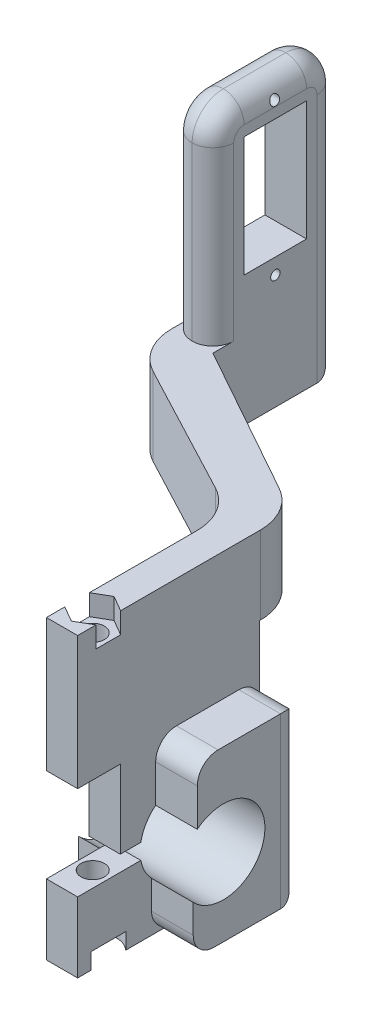
SolidWorks part; units mm, degrees
ref_plane "Front Plane" through (0, 0, 0) normal (0, 0, 1) x (1, 0, 0)
ref_plane "Top Plane" through (0, 0, 0) normal (0, 1, 0) x (1, 0, 0)
ref_plane "Right Plane" through (0, 0, 0) normal (1, 0, 0) x (0, 0, -1)
sketch "Sketch1" plane through (0, 0, 0) normal (1, 0, 0) x (0, 0, -1)
  line L0 (-55.3503, -42.4114) -> (-43.2084, -42.4114)
  line L2 (4.6497, -1.9114) -> (4.6497, 37.0886)
  line L3 (4.6497, 37.0886) -> (28.6497, 37.0886)
  line L4 (10.6497, 31.0886) -> (22.6497, 31.0886)
  line L5 (-27.3711, -35.4334) -> (28.6497, 37.0886) construction
  line L6 (4.6497, 37.0886) -> (-5.2585, -41.9446) construction
  line L7 (-20.3503, -58.9114) -> (-55.3503, -58.9114)
  line L8 (-55.3503, -45.4114) -> (-43.2084, -45.4114)
  line L10 (-55.3503, -58.9114) -> (-55.3503, -45.4114)
  line L11 (10.6497, 31.0886) -> (10.6497, 8.0886)
  line L12 (28.6497, 37.0886) -> (28.6497, -16.9114)
  line L13 (10.6497, 8.0886) -> (22.6497, 8.0886)
  line L14 (22.6497, 31.0886) -> (22.6497, 8.0886)
  line L15 (-55.3503, -42.4114) -> (-55.3503, -28.9114)
  line L18 (28.6497, -16.9114) -> (-20.3503, -16.9114)
  line L19 (4.6497, -1.9114) -> (-55.3503, -1.9114)
  line L20 (-55.3503, -28.9114) -> (-55.3503, -1.9114)
  line L21 (-20.3503, -58.9114) -> (-20.3503, -16.9114)
  arc A0 (-43.2084, -45.4114) -> (-43.2084, -42.4114) centre (-35.3503, -43.9114) ccw
  circle A1 centre (16.6497, 34.0886) radius 0.9
  circle A2 centre (16.6497, 5.0886) radius 0.9
  point P0 (0, 0)
  dimension "D3" = 16
  dimension "D11" = 1.8
  dimension "D12" = 1.8
  dimension "D1" = 30
  dimension "D2" = 15
  dimension "D4" = 35
  dimension "D5" = 20
  dimension "D6" = 24
  dimension "D7" = 12
  dimension "D8" = 6
  dimension "D9" = 6
  dimension "D10" = 23
  dimension "D13" = 3
  dimension "D14" = 3
  dimension "D15" = 6
  dimension "D16" = 6
  dimension "D17" = 13.5
  dimension "D18" = 3
  dimension "D19" = 86
  dimension "D20" = 25
  dimension "D21" = 42
  dimension "D22" = 60
extrude "Boss-Extrude1" add sketch "Sketch1" along normal blind 42
hole_wizard "CBORE for M4 Pan Head Machine Screw2" positions "Sketch6" profile "Sketch5" counterbore size "M4" standard "ANSI Metric" end condition through all
sketch "Sketch6" plane through (0, -58.9114, 0) normal (0, -1, 0) x (-1, 0, 0)
  line L0 (-42, -55.3503) -> (0, -55.3503) construction
  line L2 (-42, -55.3503) -> (-42, -20.3503) construction
  point P0 (-39, -49.4503)
  dimension "D1" = 5.9
  dimension "D2" = 3
sketch "Sketch5" plane through (39, -58.9114, 49.4503) normal (1, 0, 0) x (0, 0, -1)
  line L0 (0, 0) -> (0, 96)
  line L1 (0, 96) -> (2.25, 96)
  line L3 (2.25, 96) -> (2.25, 3.1)
  line L4 (2.25, 3.1) -> (4.5, 3.1)
  line L5 (4.5, 3.1) -> (4.5, 0)
  line L7 (4.5, 0) -> (0, 0)
  line L11 (0, -6.35) -> (0, 107.95) construction
  dimension "Thru Hole Dia." = 4.5
  dimension "Thru Hole Depth" = 96
  dimension "C'Bore Dia." = 9
  dimension "C'Bore Depth" = 3.1
sketch "Sketch7" plane through (0, -1.9114, 0) normal (0, 1, 0) x (1, 0, 0)
  line L0 (42, 4.6497) -> (42, -55.3503) construction
  line L1 (42.55, -51.4999) -> (42.55, -47.4007)
  line L2 (42.55, -47.4007) -> (39, -45.3511)
  line L3 (39, -45.3511) -> (35.45, -47.4007)
  line L4 (35.45, -47.4007) -> (35.45, -51.4999)
  line L5 (35.45, -51.4999) -> (39, -53.5495)
  line L6 (39, -53.5495) -> (42.55, -51.4999)
  circle A0 centre (39, -49.4503) radius 3.55 construction
  dimension "D1" = 7.1
  dimension "D2" = 0
extrude "Cut-Extrude2" cut sketch "Sketch7" against normal blind 4
sketch "Sketch11" plane through (0, 0, 0) normal (-1, 0, 0) x (0, 0, 1)
  line L1 (55.3503, -1.9114) -> (20.3503, -1.9114)
  line L2 (55.3503, -1.9114) -> (55.3503, -58.9114)
  line L3 (55.3503, -58.9114) -> (20.3503, -58.9114)
  line L4 (20.3503, -1.9114) -> (20.3503, -58.9114)
extrude "Cut-Extrude3" cut sketch "Sketch11" against normal blind 36
sketch "Sketch12" plane through (42, 0, 0) normal (1, 0, 0) x (0, 0, -1)
  line L1 (4.6497, 37.0886) -> (28.6497, 37.0886)
  line L2 (4.6497, 37.0886) -> (4.6497, -16.9114)
  line L3 (4.6497, -16.9114) -> (28.6497, -16.9114)
  line L4 (28.6497, 37.0886) -> (28.6497, -16.9114)
extrude "Cut-Extrude4" cut sketch "Sketch12" against normal blind 34
sketch "Sketch13" plane through (36, 0, 0) normal (-1, 0, 0) x (0, 0, 1)
  line L0 (40.3503, -37.6664) -> (40.3503, -26.4405)
  line L1 (40.3503, -26.4405) -> (20.3503, -26.4405)
  line L2 (20.3503, -16.9114) -> (20.3503, -58.9114) construction
  line L3 (20.3503, -26.4405) -> (20.3503, -58.9114)
  line L4 (20.3503, -58.9114) -> (41.1345, -58.9114)
  line L5 (20.3503, -58.9114) -> (46.0962, -58.9114) construction
  line L6 (41.1345, -58.9114) -> (41.1345, -49.438)
  arc A0 (40.3503, -37.6664) -> (41.1345, -49.438) centre (35.3503, -43.9114) ccw
  dimension "D2" = 8
  dimension "D1" = 20
extrude "Boss-Extrude2" add sketch "Sketch13" along normal blind 8 and the other way blind 14
fillet "Fillet3" radius 4 9 edges at (32, -26.4405, 40.3503) (32, -58.9114, 41.1345) (46, -58.9114, 41.1345) (46, -26.4405, 40.3503) (32, -26.4405, 20.3503) (28, -42.6759, 20.3503) (39, -58.9114, 20.3503) (46, -26.4405, 20.3503) (50, -42.6759, 20.3503)
sketch "Sketch14" plane through (42, 0, 0) normal (1, 0, 0) x (0, 0, -1)
  line L0 (-55.3503, -42.4114) -> (-43.2084, -42.4114) construction
  line L1 (-47.1503, -27.4114) -> (-55.3503, -27.4114)
  line L2 (-47.1503, -27.4114) -> (-47.1503, -42.4114)
  line L3 (-47.1503, -42.4114) -> (-55.3503, -42.4114)
  line L4 (-55.3503, -27.4114) -> (-55.3503, -42.4114)
  line L5 (-55.3503, -1.9114) -> (-55.3503, -42.4114) construction
  dimension "D1" = 0
  dimension "D2" = 0
  dimension "D3" = 15
  dimension "D4" = 8.2
extrude "Cut-Extrude5" cut sketch "Sketch14" against normal through all
fillet "Fillet4" radius 6 2 edges at (4, 37.0886, -4.6497) (4, 37.0886, -28.6497)
fillet "Fillet5" radius 4 11 edges at (0, 14.5886, -4.6497) (0, 35.3312, -6.4071) (0, 37.0886, -16.6497) (0, 35.3312, -26.8923) (8, 14.5886, -4.6497) (8, 35.3312, -6.4071) (8, 37.0886, -16.6497) (8, 35.3312, -26.8923) (0, 7.0886, -28.6497) (8, 7.0886, -28.6497) (4, -16.9114, -28.6497)
sketch "Sketch15" plane through (0, -1.9114, 0) normal (0, 1, 0) x (1, 0, 0)
  line L0 (36, -20.3503) -> (0, -1.3503)
  line L1 (0, 8.6497) -> (0, -20.3503) construction
  line L2 (0, -1.3503) -> (0, -20.3503)
  line L3 (0, -20.3503) -> (36, -20.3503)
  line L4 (8, 4.6497) -> (42, -14.3503)
  line L5 (42, 4.6497) -> (42, -47.0832) construction
  line L6 (42, -14.3503) -> (42, 4.6497)
  line L7 (42, 4.6497) -> (8, 4.6497)
  dimension "D1" = 6
  dimension "D2" = 6
extrude "Cut-Extrude6" cut sketch "Sketch15" against normal through all
fillet "Fillet6" radius 10 3 edges at (42, -9.4114, 14.3503) (36, -9.4114, 20.3503) (0, -9.4114, 1.3503)
